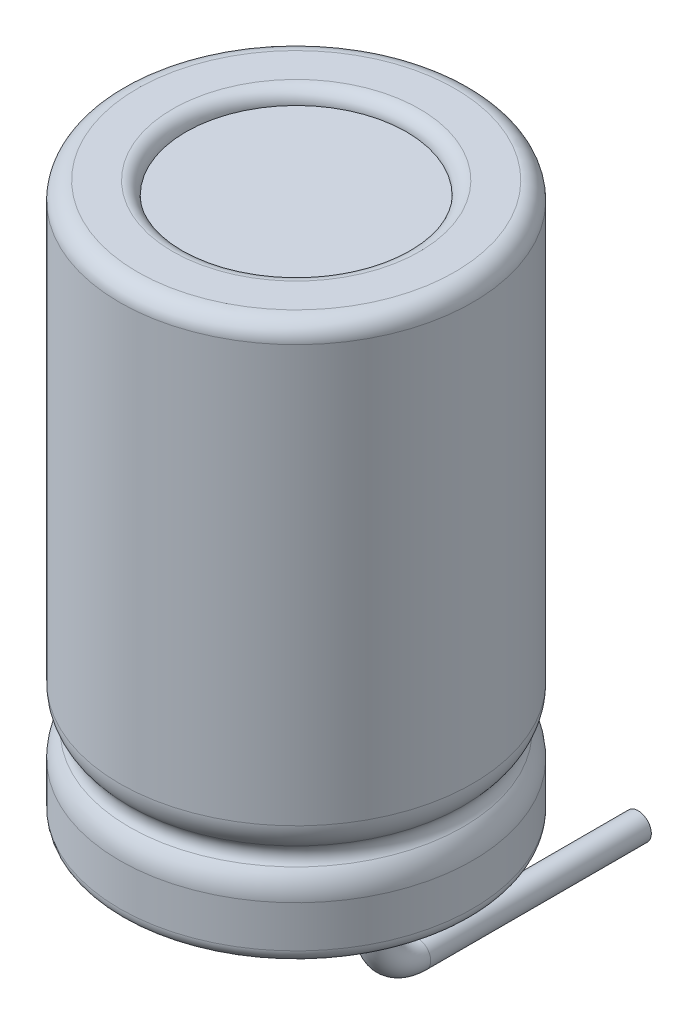
SolidWorks part; units mm, degrees
ref_plane "Front Plane" through (0, 0, 0) normal (0, 0, 1) x (1, 0, 0)
ref_plane "Top Plane" through (0, 0, 0) normal (0, 1, 0) x (1, 0, 0)
ref_plane "Right Plane" through (0, 0, 0) normal (1, 0, 0) x (0, 0, -1)
sketch "Эскиз2" plane through (0, 0, 0) normal (0, 1, 0) x (1, 0, 0)
  circle A0 centre (0, 0) radius 4
  dimension "D1" = 8
extrude "Бобышка-Вытянуть1" add sketch "Эскиз2" along normal blind 12.6
sketch "Эскиз3" plane through (0, 0, 0) normal (0, -1, 0) x (1, 0, 0)
  circle A0 centre (0, 0) radius 2.5
  dimension "D1" = 5
extrude "Вырез-Вытянуть1" cut sketch "Эскиз3" against normal blind 0.3
sketch "Эскиз4" plane through (0, 0.3, 0) normal (0, -1, 0) x (1, 0, 0)
  line L0 (0, 3.1513) -> (0, -3.4223) construction
  line L1 (-3.3944, 0) -> (3.3545, 0) construction
  circle A0 centre (-1.75, 0) radius 0.3
  dimension "D1" = 0.6
  dimension "D2" = 1.75
ref_plane "Плоскость1" through (-1.75, 0, 0) normal (-1, 0, 0) x (0, 0, 1)
sketch "Эскиз6" plane through (-1.75, 0, 0) normal (-1, 0, 0) x (0, 0, 1)
  line L0 (0, 0.3) -> (0, -1.2)
  line L1 (-0.3, 0.3) -> (0.3, 0.3) construction
  line L2 (-1, -2.2) -> (-6, -2.2)
  arc A0 (-1, -2.2) -> (0, -1.2) centre (-1, -1.2) ccw
  point P8 (0, -2.2)
  dimension "D3" = 1
  dimension "D1" = 2.5
  dimension "D2" = 6
sweep "По траектории1" add profiles "Эскиз4" path "Эскиз6"
mirror "Зеркальное отражение1" about plane through (0, 0, 0) normal (1, 0, 0) of bodies 103
sketch "Эскиз7" plane through (0, 12.6, 0) normal (0, 1, 0) x (1, 0, 0)
  circle A0 centre (0, 0) radius 2.5
  dimension "D1" = 5
extrude "Вырез-Вытянуть2" cut sketch "Эскиз7" against normal blind 0.3
sketch "Эскиз9" plane through (0, 0, 0) normal (1, 0, 0) x (0, 0, -1)
  line L0 (-4, 12.6) -> (-4, 0) construction
  line L1 (-4, 12.6) -> (-4, 0) construction
  line L2 (-4, 12.6) -> (-4, 0) construction
  line L3 (0, -2.3692) -> (0, 14.89) construction
  line L4 (-4, 2.3) -> (-4, 1.7)
  arc A0 (-4, 2.3) -> (-4, 1.7) centre (-4, 2) cw
  dimension "D2" = 0.3
  dimension "D1" = 2
revolve "Вырез-Повернуть1" cut sketch "Эскиз9" angle 360 about L3
fillet "Скругление1" radius 0.3 1 edges at (0, 0, -2.5)
fillet "Скругление2" radius 0.8 2 edges at (0, 2.3, -4) (0, 1.7, -4)
fillet "Скругление3" radius 0.4 1 edges at (0, 12.6, 4)
fillet "Скругление4" radius 0.3 1 edges at (0, 12.6, 2.5)
fillet "Скругление5" radius 0.3 1 edges at (0, 0, 4)
